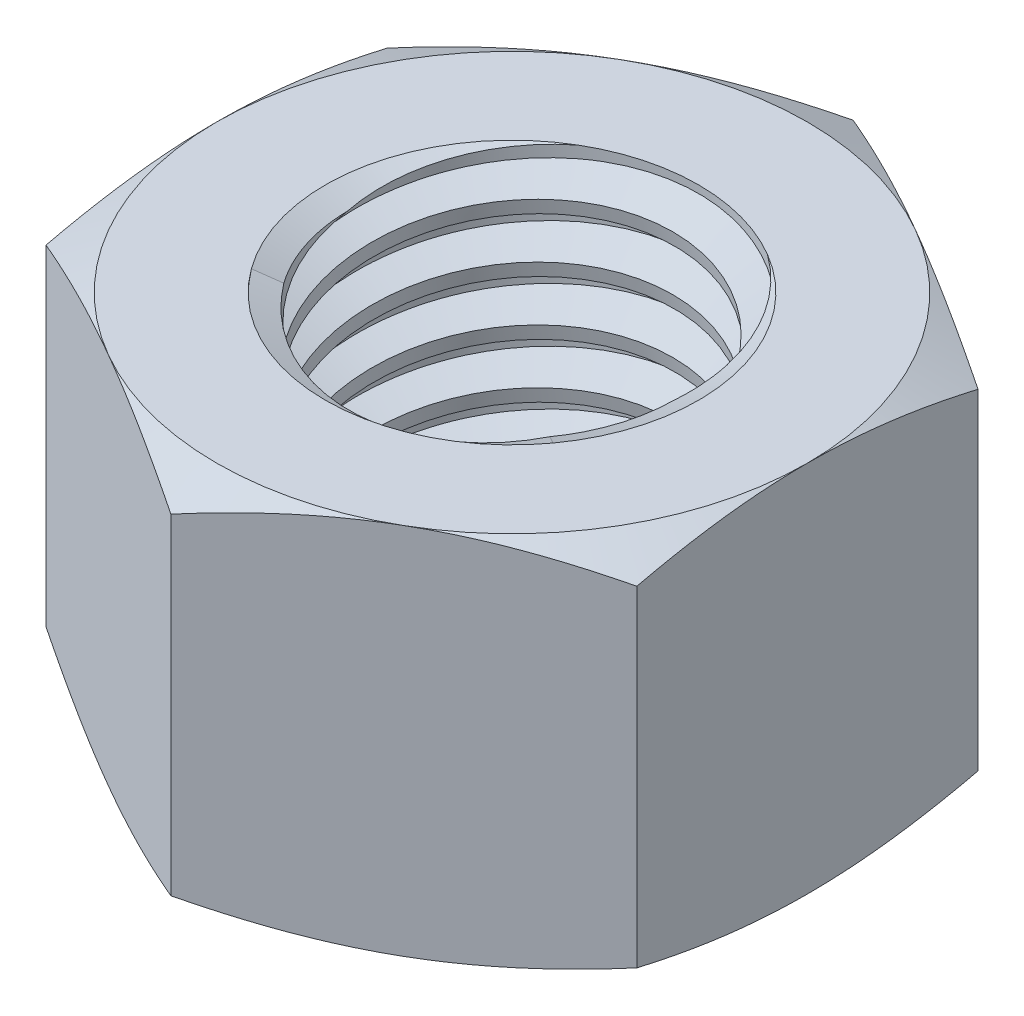
SolidWorks part; units mm, degrees
ref_plane "Front" through (0, 0, 0) normal (0, 0, 1) x (1, 0, 0)
ref_plane "Top" through (0, 0, 0) normal (0, 1, 0) x (1, 0, 0)
ref_plane "Right" through (0, 0, 0) normal (1, 0, 0) x (0, 0, -1)
sketch "Sketch1" plane through (0, 0, 0) normal (0, 1, 0) x (1, 0, 0)
  line L1 (0, 10.9697) -> (-9.5, 5.4848)
  line L2 (-9.5, 5.4848) -> (-9.5, -5.4848)
  line L3 (-9.5, -5.4848) -> (0, -10.9697)
  line L4 (0, -10.9697) -> (9.5, -5.4848)
  line L5 (9.5, -5.4848) -> (9.5, 5.4848)
  line L6 (9.5, 5.4848) -> (0, 10.9697)
  circle A0 centre (0, 0) radius 9.5 construction
  dimension "Hex Flats" = 19
extrude "Extrude1" add sketch "Sketch1" along normal mid plane 12
sketch "Sketch2" plane through (0, 0, 0) normal (1, 0, 0) x (0, 0, -1)
  line L0 (-6, -6) -> (-6, 6) construction
  line L1 (0, -6) -> (6, -6)
  line L2 (0, -6) -> (0, 6)
  line L3 (0, 6) -> (6, 6)
  line L4 (6, -6) -> (6, 6)
  line L5 (-5.4848, 6) -> (5.4848, 6) construction
  line L6 (-5.4848, -6) -> (5.4848, -6) construction
  line L7 (0, -12) -> (0, -6) construction
  dimension "Thread Dia" = 12
revolve "Revolve1" add sketch "Sketch2" angle 360 about L7
sketch "Sketch3" plane through (0, 0, 0) normal (1, 0, 0) x (0, 0, -1)
  line L0 (6, 6) -> (-6, 6) construction
  line L1 (-6, 6) -> (-6, 4.25) construction
  line L2 (-6, 4.25) -> (6, 6) construction
  line L3 (6, 6) -> (6.0316, 5.7835) construction
  line L4 (6.0316, 5.7835) -> (6.2525, 4.2683)
  line L5 (6.2525, 4.2683) -> (5.2363, 4.6728)
  line L6 (5.2363, 4.6728) -> (5.1732, 5.1057)
  line L7 (5.1732, 5.1057) -> (6.0316, 5.7835)
  line L8 (5.2048, 4.8892) -> (6.1421, 5.0259) construction
  line L9 (6, 6) -> (6, 5.0052) construction
  line L10 (6, 5.0052) -> (-6, 3.2552) construction
  line L11 (-6, 3.2552) -> (-6, 4.25) construction
  line L12 (-0.2727, 6) -> (0.2727, 2.2604) construction
  line L13 (-6, -6) -> (-6, 6) construction
  line L14 (0, 6) -> (6, 6) construction
  line L15 (6, -6) -> (6, 6) construction
  line L16 (0, 0) -> (0, 6) construction
  line L17 (-6.0316, 5.7835) -> (-6.2525, 4.2683) construction
  line L18 (-5.1732, 5.1057) -> (-6.0316, 5.7835) construction
  line L19 (-5.2363, 4.6728) -> (-5.1732, 5.1057) construction
  line L20 (-6.2525, 4.2683) -> (-5.2363, 4.6728) construction
  line L21 (0.2727, 6) -> (-0.2727, 2.2604) construction
  point P13 (0, 4.1302)
  dimension "D1" = 0.2188
  dimension "D2" = 0.4375
  dimension "Thread Pitch" = 1.75
  dimension "D4" = 60
  dimension "D5" = 1.75
revolve "Cut-Revolve1" cut sketch "Sketch3" angle 360 about L12
pattern_linear "LPattern1" count 7 spacing 1.75 along (0, -1, 0) count 2 spacing 1.75 along (0, 1, 0) of "Cut-Revolve1"
sketch "Sketch4" plane through (0, 0, 0) normal (1, 0, 0) x (0, 0, -1)
  line L0 (0, 6) -> (6, 6)
  line L1 (6, 6) -> (5.1732, 5.6144)
  line L2 (5.1732, 5.6144) -> (5.1732, -5.6144)
  line L3 (5.1732, -5.6144) -> (6, -6)
  line L4 (6, -6) -> (0, -6)
  line L5 (0, -6) -> (0, 6)
  line L6 (6, -6) -> (6, 6) construction
  line L7 (0, 6) -> (6, 6) construction
  line L8 (0, -6) -> (6, -6) construction
  line L9 (0, -6) -> (0, 6) construction
  line L10 (0, 6) -> (0, 6.9123) construction
  dimension "D1" = 25
revolve "Cut-Revolve2" cut sketch "Sketch4" angle 360 about L10
combine bodies "Combine1" operation type subtract main body 112 bodies to subtract 111
sketch "Sketch5" plane through (0, 0, 0) normal (1, 0, 0) x (0, 0, -1)
  line L0 (0, -6) -> (9.5, -6)
  line L1 (9.5, -6) -> (10.9697, -5.3147)
  line L2 (10.9697, -5.3147) -> (10.9697, 5.3147)
  line L3 (10.9697, 5.3147) -> (9.5, 6)
  line L4 (0, 6) -> (0, 7.27)
  line L5 (0, 7.27) -> (12.2397, 7.27)
  line L6 (12.2397, 7.27) -> (12.2397, -7.27)
  line L7 (12.2397, -7.27) -> (0, -7.27)
  line L8 (0, -7.27) -> (0, -6)
  line L9 (9.5, 6) -> (9.5, -6) construction
  line L11 (0, -6) -> (6, -6) construction
  line L12 (9.5, 6) -> (0, 6)
  line L13 (10.9697, 0) -> (12.2397, 0) construction
  line L14 (10.9697, 6) -> (10.9697, -6) construction
  line L15 (0, -6) -> (0, 6) construction
  line L17 (0, 0) -> (9.5, 0) construction
  line L22 (0, 6) -> (6, 6) construction
  dimension "D1" = 25
  dimension "D2" = 1.27
  dimension "D3" = 12
revolve "Cut-Revolve3" cut sketch "Sketch5" angle 360 about L15
equation "\"D1@Sketch3\"=\"Thread Pitch@Sketch3\"/8"
equation "\"D2@Sketch3\"=\"Thread Pitch@Sketch3\"/4"
equation "\"D5@Sketch3\"=\"Thread Pitch@Sketch3\""
equation "\"D4@LPattern1\"=\"Thread Pitch@Sketch3\""
equation "\"D3@LPattern1\"=\"Thread Pitch@Sketch3\""
equation "\"D1@LPattern1\"=\"Height@Extrude1\"/\"Thread Pitch@Sketch3\""
